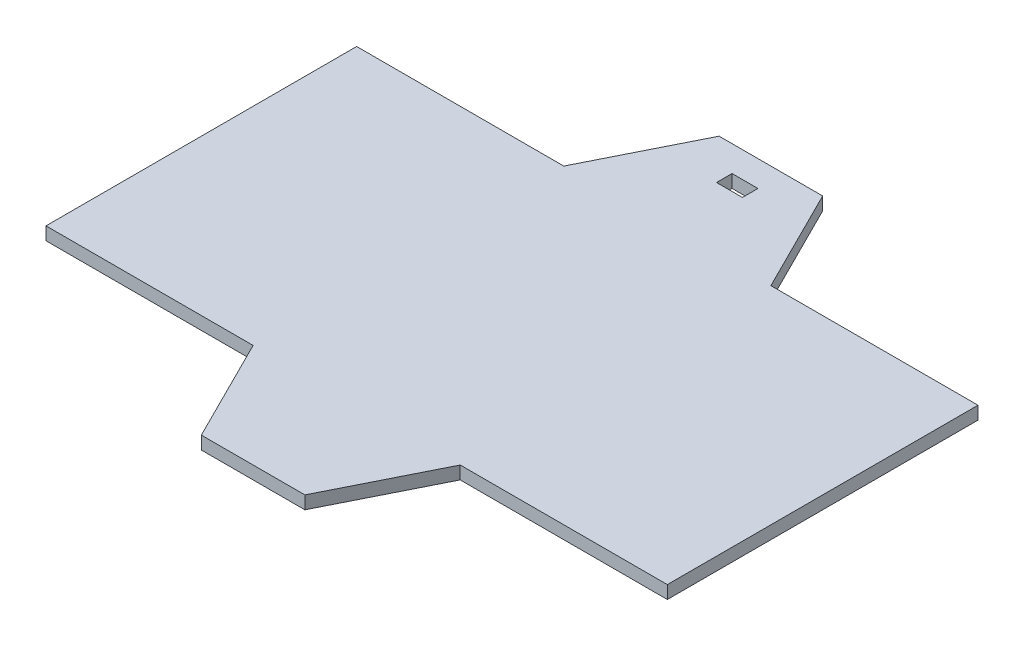
SolidWorks part; units mm, degrees
ref_plane "Front Plane" through (0, 0, 0) normal (0, 0, 1) x (1, 0, 0)
ref_plane "Top Plane" through (0, 0, 0) normal (0, 1, 0) x (1, 0, 0)
ref_plane "Right Plane" through (0, 0, 0) normal (1, 0, 0) x (0, 0, -1)
sketch "Sketch1" plane through (0, 0, 0) normal (0, 1, 0) x (1, 0, 0)
  line L0 (0, 0) -> (0, 152.4)
  line L13 (0, 152.4) -> (101.6, 152.4)
  line L16 (203.2, 152.4) -> (304.8, 152.4)
  line L17 (304.8, 152.4) -> (304.8, 0)
  line L18 (304.8, 0) -> (203.2, 0)
  line L21 (101.6, 0) -> (0, 0)
  line L22 (101.6, 152.4) -> (127, 203.2)
  line L23 (127, 203.2) -> (177.8, 203.2)
  line L24 (177.8, 203.2) -> (203.2, 152.4)
  line L25 (101.6, 0) -> (127, -50.8)
  line L26 (127, -50.8) -> (177.8, -50.8)
  line L27 (177.8, -50.8) -> (203.2, 0)
  dimension "D1" = 304.8
  dimension "D2" = 152.4
  dimension "D3" = 101.6
  dimension "D4" = 101.6
  dimension "D5" = 50.8
  dimension "D6" = 50.8
  dimension "D7" = 50.8
extrude "Boss-Extrude1" add sketch "Sketch1" along normal blind 6.35
sketch "Sketch2" plane through (0, 6.35, 0) normal (0, 1, 0) x (1, 0, 0)
  line L0 (177.8, 203.2) -> (127, 203.2) construction
  line L1 (158.75, 182.88) -> (146.05, 182.88)
  line L2 (158.75, 182.88) -> (158.75, 190.5)
  line L3 (158.75, 190.5) -> (146.05, 190.5)
  line L4 (146.05, 182.88) -> (146.05, 190.5)
  point P6 (152.4, 203.2)
  dimension "D1" = 12.7
  dimension "D2" = 7.62
  dimension "D3" = 12.7
  dimension "D4" = 19.05
extrude "Cut-Extrude1" cut sketch "Sketch2" against normal through all contours L2 L3 L4 L1
